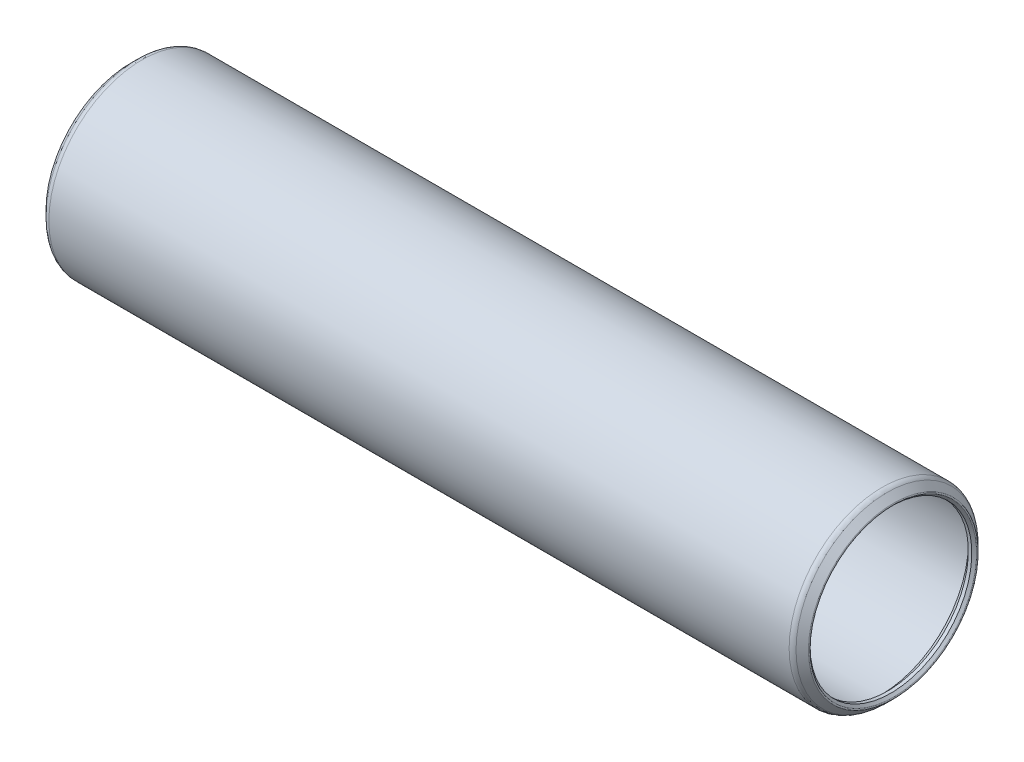
SolidWorks part; units mm, degrees
material "AISI 304"
ref_plane "Front Plane" through (0, 0, 0) normal (0, 0, 1) x (1, 0, 0)
ref_plane "Top Plane" through (0, 0, 0) normal (0, 1, 0) x (1, 0, 0)
ref_plane "Right Plane" through (0, 0, 0) normal (1, 0, 0) x (0, 0, -1)
ref_plane "Plane1" through (82.7151, 0, 0) normal (1, 0, 0) x (0, 0, -1)
sketch "Sketch1" plane through (0, 0, 0) normal (0, 0, 1) x (1, 0, 0)
  line L0 (-0.6395, 9.1676) -> (-0.381, 8.9091)
  line L1 (-0.381, 8.9091) -> (0, 8.9091)
  line L2 (0, 8.9091) -> (0.762, 9.671)
  line L3 (0.762, 9.671) -> (81.9531, 9.671)
  line L4 (81.9531, 9.671) -> (82.7151, 8.9091)
  line L5 (82.7151, 8.9091) -> (83.0961, 8.9091)
  line L6 (83.0961, 8.9091) -> (83.3546, 9.1676)
  line L7 (83.3546, 9.3472) -> (82.6697, 10.0321)
  line L8 (82.1309, 10.2553) -> (0.5842, 10.2553)
  line L9 (0.0454, 10.0321) -> (-0.6395, 9.3472)
  line L10 (82.7151, 0) -> (0, 0) construction
  arc A0 (-0.6395, 9.3472) -> (-0.6395, 9.1676) centre (-0.5497, 9.2574) ccw
  arc A1 (83.3546, 9.1676) -> (83.3546, 9.3472) centre (83.2648, 9.2574) ccw
  arc A2 (82.6697, 10.0321) -> (82.1309, 10.2553) centre (82.1309, 9.4933) ccw
  arc A3 (0.5842, 10.2553) -> (0.0454, 10.0321) centre (0.5842, 9.4933) ccw
revolve "Revolve1" add sketch "Sketch1" angle 360 about L10 reverse direction yes
ref_plane "Plane2" through (41.3576, 0, 0) normal (1, 0, 0) x (0, 0, -1)
ref_plane "cp1 XY" through (41.3576, 0, 0) normal (1, 0, 0) x (0, 0, -1)
ref_plane "cp1 XZ" through (0, 10.2553, 0) normal (0, -1, 0) x (-1, 0, 0)
ref_plane "cp1 YZ" through (0, 0, 0) normal (0, 0, -1) x (-1, 0, 0)
ref_axis "cp1 X" through (41.3576, 10.2553, 80.9) along (0, 0, -1)
ref_axis "cp1 Y" through (41.3576, -50, 0) along (0, 1, 0)
ref_axis "cp1 Z" through (80.9, 10.2553, 0) along (-1, 0, 0)
sketch3d "cp1"
  point P0 (41.3576, 10.2553, 0)
ref_plane "cp2 XY" through (41.3576, 0, 0) normal (1, 0, 0) x (0, 0, -1)
ref_plane "cp2 XZ" through (0, 0, 0) normal (0, -1, 0) x (-1, 0, 0)
ref_plane "cp2 YZ" through (0, 0, -10.2553) normal (0, 0, -1) x (-1, 0, 0)
ref_axis "cp2 X" through (41.3576, 0, 80.9) along (0, 0, -1)
ref_axis "cp2 Y" through (41.3576, -50, -10.2553) along (0, 1, 0)
ref_axis "cp2 Z" through (80.9, 0, -10.2553) along (-1, 0, 0)
sketch3d "cp2"
  point P0 (41.3576, 0, -10.2553)
ref_plane "cp3 XY" through (41.3576, 0, 0) normal (1, 0, 0) x (0, 0, -1)
ref_plane "cp3 XZ" through (0, -10.2553, 0) normal (0, -1, 0) x (-1, 0, 0)
ref_plane "cp3 YZ" through (0, 0, 0) normal (0, 0, -1) x (-1, 0, 0)
ref_axis "cp3 X" through (41.3576, -10.2553, 80.9) along (0, 0, -1)
ref_axis "cp3 Y" through (41.3576, -50, 0) along (0, 1, 0)
ref_axis "cp3 Z" through (80.9, -10.2553, 0) along (-1, 0, 0)
sketch3d "cp3"
  point P0 (41.3576, -10.2553, 0)
ref_plane "cp4 XY" through (41.3576, 0, 0) normal (1, 0, 0) x (0, 0, -1)
ref_plane "cp4 XZ" through (0, 0, 0) normal (0, -1, 0) x (-1, 0, 0)
ref_plane "cp4 YZ" through (0, 0, 10.2553) normal (0, 0, -1) x (-1, 0, 0)
ref_axis "cp4 X" through (41.3576, 0, 80.9) along (0, 0, -1)
ref_axis "cp4 Y" through (41.3576, -50, 10.2553) along (0, 1, 0)
ref_axis "cp4 Z" through (80.9, 0, 10.2553) along (-1, 0, 0)
sketch3d "cp4"
  point P0 (41.3576, 0, 10.2553)
ref_plane "tube_front XY" through (0, 0, 0) normal (1, 0, 0) x (0, 0, -1)
ref_plane "tube_front XZ" through (0, 0, 0) normal (0, -1, 0) x (-1, 0, 0)
ref_plane "tube_front YZ" through (0, 0, 0) normal (0, 0, -1) x (-1, 0, 0)
ref_axis "tube_front X" through (0, 0, 80.9) along (0, 0, -1)
ref_axis "tube_front Y" through (0, -50, 0) along (0, 1, 0)
ref_axis "tube_front Z" through (80.9, 0, 0) along (-1, 0, 0)
sketch3d "tube_front"
  point P0 (0, 0, 0)
ref_plane "tube_rear XY" through (82.7151, 0, 0) normal (1, 0, 0) x (0, 0, -1)
ref_plane "tube_rear XZ" through (0, 0, 0) normal (0, -1, 0) x (-1, 0, 0)
ref_plane "tube_rear YZ" through (0, 0, 0) normal (0, 0, -1) x (-1, 0, 0)
ref_axis "tube_rear X" through (82.7151, 0, 80.9) along (0, 0, -1)
ref_axis "tube_rear Y" through (82.7151, -50, 0) along (0, 1, 0)
ref_axis "tube_rear Z" through (80.9, 0, 0) along (-1, 0, 0)
sketch3d "tube_rear"
  point P0 (82.7151, 0, 0)
